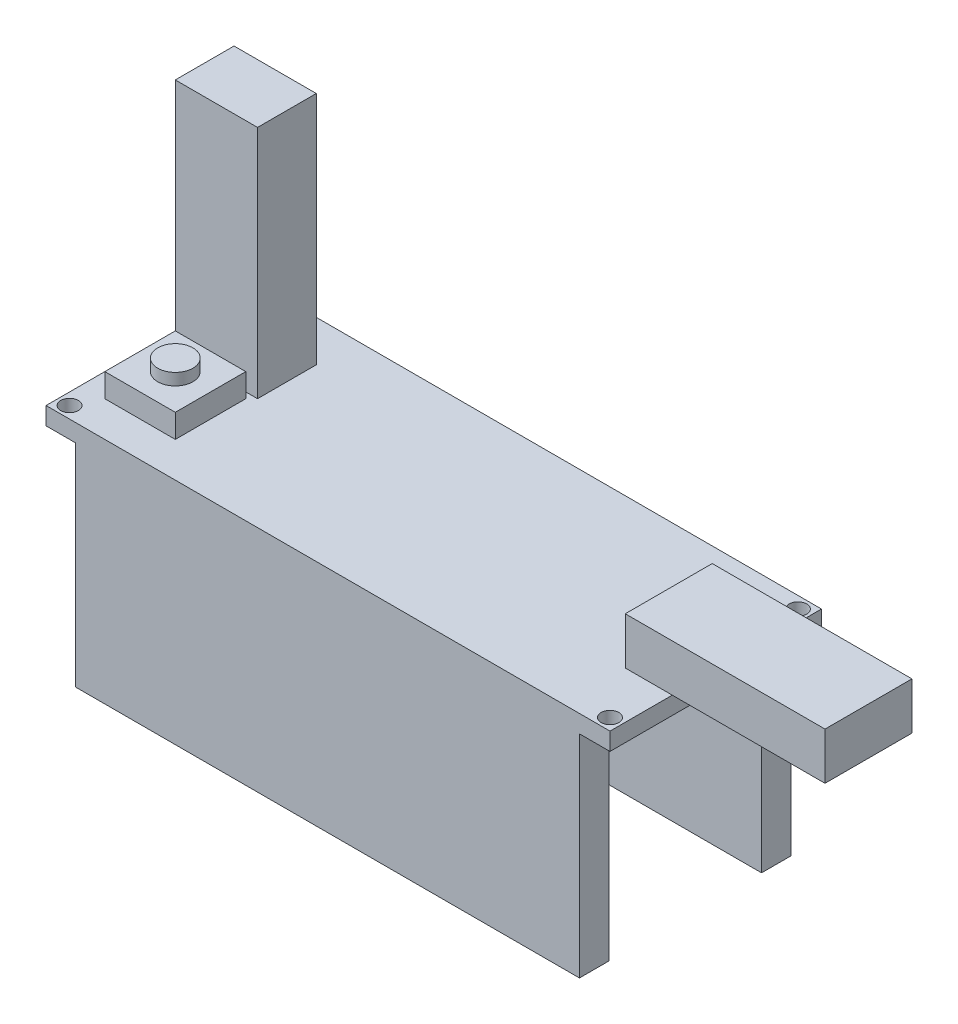
SolidWorks part; units mm, degrees
ref_plane "Спереди" through (0, 0, 0) normal (0, 0, 1) x (1, 0, 0)
ref_plane "Сверху" through (0, 0, 0) normal (0, 1, 0) x (1, 0, 0)
ref_plane "Справа" through (0, 0, 0) normal (1, 0, 0) x (0, 0, -1)
sketch "Эскиз1" plane through (0, 0, 0) normal (0, 1, 0) x (1, 0, 0)
  line L0 (0, 0) -> (-48, 0)
  line L1 (-48, 0) -> (-48, 18)
  line L2 (-48, 18) -> (0, 18)
  line L3 (0, 18) -> (0, 0)
extrude "Бобышка-Вытянуть1" add sketch "Эскиз1" along normal blind 1.5
sketch "Эскиз2" plane through (0, 1.5, 0) normal (0, 1, 0) x (1, 0, 0)
  line L0 (0, 9) -> (0, 12.7)
  line L1 (0, 0) -> (0, 18) construction
  line L2 (0, 12.7) -> (-4, 12.7)
  line L3 (-4, 12.7) -> (-4, 5.3)
  line L4 (-4, 5.3) -> (13, 5.3)
  line L5 (13, 5.3) -> (13, 12.7)
  line L6 (13, 12.7) -> (0, 12.7)
  line M1 (0, 0) -> (0, 18)
extrude "Бобышка-Вытянуть2" add sketch "Эскиз2" along normal blind 4 contours L5 L6 L4 M1 | L3 L4 L2 M1 region at (-2, 1.5, -9) region at (6.5, 1.5, -9)
sketch "Эскиз4" plane through (0, 0, 0) normal (0, -1, 0) x (-1, 0, 0)
  line L0 (0, 18) -> (2.6, 18)
  line L1 (0, 18) -> (48, 18) construction
  line L2 (48, 18) -> (45.5, 18)
  line L3 (45.5, 18) -> (2.6, 18)
  line L4 (2.6, 18) -> (2.6, 15.5)
  line L5 (2.6, 15.5) -> (45.5, 15.5)
  line L6 (45.5, 15.5) -> (45.5, 18)
  line L7 (0, 9) -> (48, 9) construction
  line L10 (45.5, 2.5) -> (45.5, 0)
  line L11 (2.6, 2.5) -> (45.5, 2.5)
  line L12 (2.6, 0) -> (2.6, 2.5)
  line L13 (45.5, 0) -> (2.6, 0)
  line L14 (48, 0) -> (45.5, 0)
  line L15 (0, 0) -> (2.6, 0)
  line M2 (0, 0) -> (48, 0)
  line M4 (48, 18) -> (0, 18)
extrude "Бобышка-Вытянуть3" add sketch "Эскиз4" along normal blind 18 contours L5 L6 L4 M4 | L12 L10 L11 M2 region at (-24.05, 0, -16.75) region at (-24.05, 0, -1.25)
sketch "Эскиз5" plane through (0, 1.5, 0) normal (0, 1, 0) x (1, 0, 0)
  line L3 (-39.5, 18) -> (-39.5, 14.5)
  line L4 (0, 18) -> (-48, 18) construction
  line L5 (-39.5, 14.5) -> (-39.5, 9.5)
  line L6 (-39.5, 9.5) -> (-46.5, 9.5)
  line L7 (-46.5, 9.5) -> (-46.5, 14.5)
  line L8 (-46.5, 14.5) -> (-39.5, 14.5)
  dimension "D1" = 3.5
extrude "Бобышка-Вытянуть4" add sketch "Эскиз5" along normal blind 20 contours L8 L7 L6 L5 region at (-43, 1.5, -12)
sketch "Эскиз6" plane through (0, 1.5, 0) normal (0, 1, 0) x (1, 0, 0)
  line L0 (-48, 0) -> (-46, 0)
  line L1 (-48, 0) -> (0, 0) construction
  line L2 (-46, 0) -> (-46, 3)
  line L3 (-46, 3) -> (-46, 9)
  line L4 (-46, 9) -> (-40, 9)
  line L5 (-40, 9) -> (-40, 3)
  line L6 (-40, 3) -> (-46, 3)
extrude "Бобышка-Вытянуть5" add sketch "Эскиз6" along normal blind 2 contours L6 L5 L4 L3 region at (-43, 1.5, -6)
sketch "Эскиз7" plane through (0, 3.5, 0) normal (0, 1, 0) x (1, 0, 0)
  line L0 (-46, 9) -> (-40, 3)
  line L1 (-40, 3) -> (-40, 9)
  line L2 (-46, 9) -> (-40, 9) construction
  line L3 (-40, 9) -> (-46, 3)
  circle A0 centre (-43, 6) radius 1.5
extrude "Бобышка-Вытянуть6" add sketch "Эскиз7" along normal blind 1 contours L0 A0 L3 | A0 region at (-42.0997, 3.5, -6)
sketch "Эскиз8" plane through (0, 1.5, 0) normal (0, 1, 0) x (1, 0, 0)
  line L0 (0, 18) -> (-48, 18) construction
  line L2 (-48, 18) -> (-48, 0) construction
  line L3 (-48, 9) -> (-34.2096, 9) construction
  line L4 (-24, 18) -> (-24, -1.1436) construction
  circle A0 centre (-47, 17) radius 0.75
  circle A1 centre (-47, 1) radius 0.75
  circle A2 centre (-1, 1) radius 0.75
  circle A3 centre (-1, 17) radius 0.75
  dimension "D1" = 1
  dimension "D2" = 1
extrude "Вырез-Вытянуть1" cut sketch "Эскиз8" against normal blind 10
